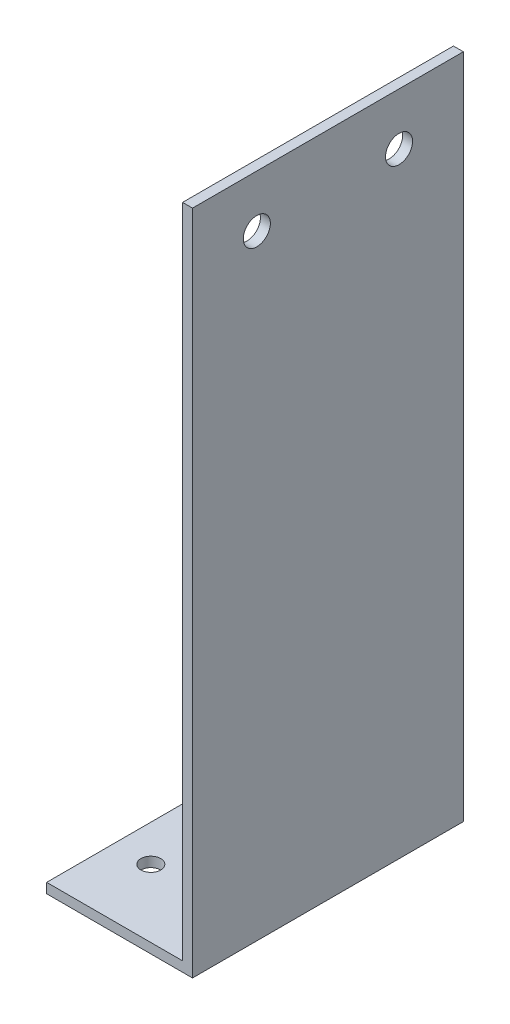
SolidWorks part; units mm, degrees
ref_plane "Alzado" through (0, 0, 0) normal (0, 0, 1) x (1, 0, 0)
ref_plane "Planta" through (0, 0, 0) normal (0, 1, 0) x (1, 0, 0)
ref_plane "Vista lateral" through (0, 0, 0) normal (1, 0, 0) x (0, 0, -1)
sketch "Croquis1" plane through (0, 0, 0) normal (0, 0, 1) x (1, 0, 0)
  line L0 (0, 0) -> (0, 320)
  line L1 (0, 0) -> (-70, 0)
  line L2 (-4.7625, 4.7625) -> (-70, 4.7625)
  line L3 (-4.7625, 4.7625) -> (-4.7625, 320)
  line L4 (-70, 0) -> (-70, 4.7625)
  line L5 (0, 320) -> (-4.7625, 320)
  dimension "D2" = 320
  dimension "D3" = 70
  dimension "D1" = 4.7625
extrude "Saliente-Extruir1" add sketch "Croquis1" along normal mid plane 130
sketch "Croquis2" plane through (0, 0, 0) normal (0, -1, 0) x (-1, 0, 0)
  line L0 (-20.5629, 0) -> (137.2136, 0) construction
  line L1 (35, -65) -> (35, 65) construction
  line L2 (70, -65) -> (0, -65) construction
  line L3 (70, 65) -> (0, 65) construction
  line L4 (52.5, -32.5) -> (17.5, -32.5) construction
  line L5 (52.5, -32.5) -> (52.5, 32.5) construction
  circle A0 centre (52.5, -32.5) radius 4.7625
  circle A1 centre (17.5, -32.5) radius 4.7625
  circle A2 centre (17.5, 32.5) radius 4.7625
  circle A3 centre (52.5, 32.5) radius 4.7625
  dimension "D1" = 9.525
  dimension "D2" = 17.5
  dimension "D3" = 32.5
  dimension "D6" = 35
  dimension "D7" = 65
  dimension "D8" = 32.5
  dimension "D4" = 2
  dimension "D5" = 2
extrude "Cortar-Extruir1" cut sketch "Croquis2" against normal blind 130
sketch "Croquis3" plane through (0, 0, 0) normal (1, 0, 0) x (0, 0, -1)
  line L0 (0, 315.912) -> (0, 117.859) construction
  line L1 (101.994, 295) -> (-93.1823, 295) construction
  line L3 (-65, 320) -> (65, 320) construction
  circle A0 centre (-34.1313, 295) radius 6.5
  circle A1 centre (34.1313, 295) radius 6.5
  dimension "D1" = 13
  dimension "D2" = 34.1313
  dimension "D3" = 25
extrude "Cortar-Extruir2" cut sketch "Croquis3" against normal blind 130
